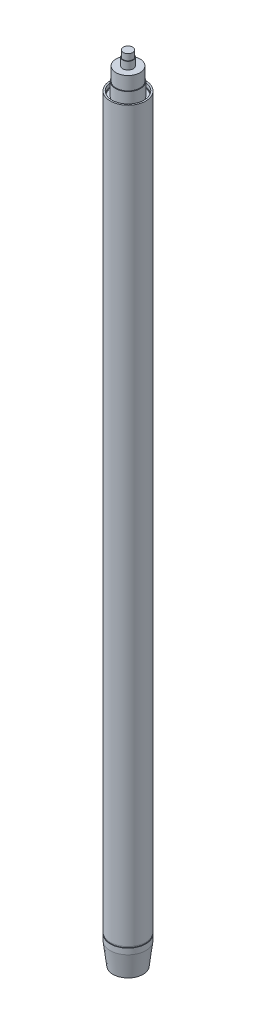
SolidWorks part; units mm, degrees
ref_plane "Front Plane" through (0, 0, 0) normal (0, 0, 1) x (1, 0, 0)
ref_plane "Top Plane" through (0, 0, 0) normal (0, 1, 0) x (1, 0, 0)
ref_plane "Right Plane" through (0, 0, 0) normal (1, 0, 0) x (0, 0, -1)
sketch "Sketch1" plane through (0, 0, 0) normal (0, 1, 0) x (1, 0, 0)
  circle A0 centre (0, 0) radius 26.7208
  circle A1 centre (0, 0) radius 24.3332
  dimension "D1" = 53.4416
  dimension "D2" = 2.3876
extrude "Boss-Extrude1" add sketch "Sketch1" along normal blind 1111.25
sketch "Sketch2" plane through (0, 0, 0) normal (0, 0, 1) x (1, 0, 0)
  line L0 (-26.7208, 0) -> (26.7208, 0) construction
  line L1 (22.5552, 7.112) -> (25.0952, 7.112)
  line L2 (22.5552, 7.112) -> (22.5552, 5.08)
  line L3 (22.5552, 5.08) -> (25.0952, 5.08)
  line L4 (25.0952, 7.112) -> (25.0952, 5.08)
  line L5 (24.3332, 0) -> (24.3332, 1111.25) construction
  dimension "D1" = 5.08
  dimension "D2" = 2.032
  dimension "D3" = 0.762
  dimension "D4" = 2.54
ref_axis "Axis1" through (0, 1111.25, 0) along (0, -1, 0)
revolve "Cut-Revolve1" cut sketch "Sketch2" angle 360 about axis through (0, 1111.25, 0) along (0, -1, 0)
ref_plane "Plane1" through (0, 555.625, 0) normal (0, -1, 0) x (-1, 0, 0)
mirror "Mirror1" about plane through (0, 555.625, 0) normal (0, -1, 0) of "Cut-Revolve1"
sketch "Sketch3" plane through (0, 0, 0) normal (1, 0, 0) x (0, 0, -1)
  line L0 (-26.7208, 0) -> (26.7208, 0) construction
  line L1 (25.9588, 10.795) -> (27.2288, 10.795)
  line L2 (25.9588, 10.795) -> (25.9588, 8.763)
  line L3 (25.9588, 8.763) -> (27.2288, 8.763)
  line L4 (27.2288, 10.795) -> (27.2288, 8.763)
  line L5 (26.7208, 0) -> (26.7208, 1111.25) construction
  dimension "D1" = 10.795
  dimension "D2" = 2.032
  dimension "D3" = 1.27
  dimension "D4" = 0.762
revolve "Cut-Revolve2" cut sketch "Sketch3" angle 360 about axis through (0, 1111.25, 0) along (0, -1, 0)
sketch "Sketch4" plane through (0, 0, 0) normal (0, 0, 1) x (1, 0, 0)
  line L0 (26.7208, 0) -> (22.6695, -33.147)
  line L1 (24.3332, 0) -> (20.2819, -33.147)
  line L2 (22.6695, -33.147) -> (20.2819, -33.147)
  line L3 (24.3332, 0) -> (26.7208, 0)
  dimension "D1" = 33.147
  dimension "D2" = 22.6695
revolve "Revolve2" add sketch "Sketch4" angle 360 about axis through (0, 1111.25, 0) along (0, -1, 0)
sketch "Sketch5" plane through (0, 1104.138, 0) normal (0, 1, 0) x (1, 0, 0)
  circle A0 centre (0, 0) radius 23.876
  dimension "D1" = 47.752
extrude "Boss-Extrude2" add sketch "Sketch5" against normal blind 12.7 separate body
sketch "Sketch6" plane through (0, 1104.138, 0) normal (0, 1, 0) x (1, 0, 0)
  circle A0 centre (0, 0) radius 18.034
  dimension "D1" = 36.068
extrude "Boss-Extrude4" add sketch "Sketch6" along normal blind 39.878 contours A0
sketch "Sketch7" plane through (0, 1144.016, 0) normal (0, 1, 0) x (1, 0, 0)
  circle A0 centre (0, 0) radius 7.9375
  circle A1 centre (0, 0) radius 3.175
  dimension "D1" = 6.35
  dimension "D2" = 15.875
extrude "Boss-Extrude5" add sketch "Sketch7" along normal blind 11.43
sketch "Sketch9" plane through (0, 1155.446, 0) normal (0, 1, 0) x (1, 0, 0)
  circle A0 centre (0, 0) radius 7.112
  dimension "D1" = 14.224
extrude "Boss-Extrude6" add sketch "Sketch9" along normal blind 9.398
sketch "Sketch10" plane through (0, 1104.138, 0) normal (0, 1, 0) x (1, 0, 0)
  circle A0 centre (0, 0) radius 19.05
  dimension "D1" = 38.1
extrude "Boss-Extrude7" add sketch "Sketch10" along normal blind 19.685
